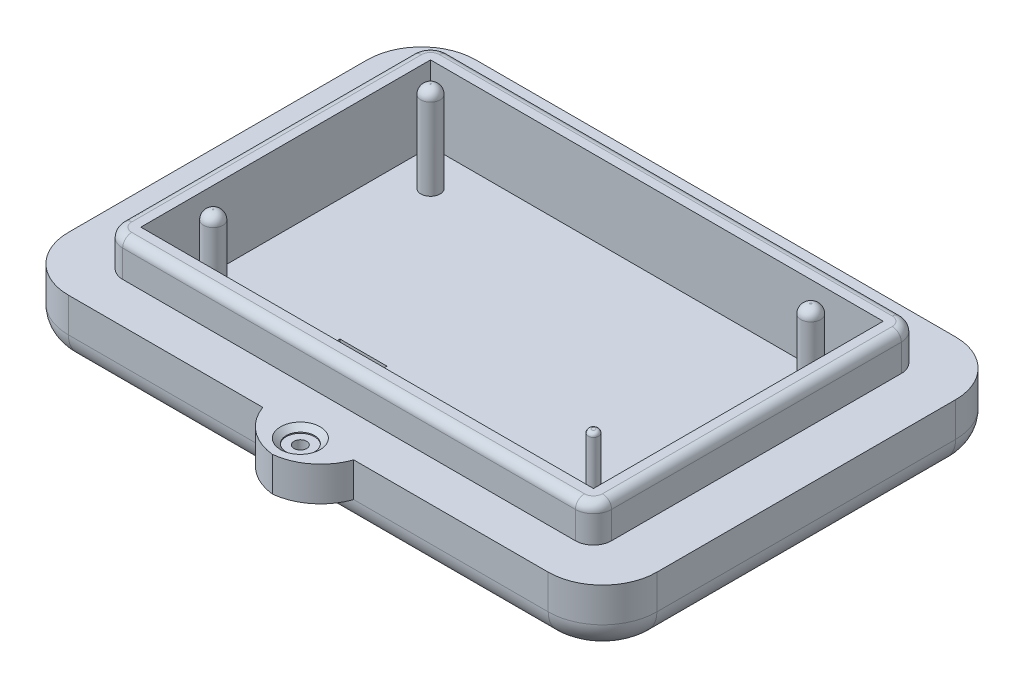
SolidWorks part; units mm, degrees
ref_plane "Front Plane" through (0, 0, 0) normal (0, 0, 1) x (1, 0, 0)
ref_plane "Top Plane" through (0, 0, 0) normal (0, 1, 0) x (1, 0, 0)
ref_plane "Right Plane" through (0, 0, 0) normal (1, 0, 0) x (0, 0, -1)
sketch "Sketch1" plane through (0, 0, 0) normal (0, 1, 0) x (1, 0, 0)
  line L1 (0, 0) -> (82.55, 0)
  line L2 (0, 0) -> (0, 57.15)
  line L3 (0, 57.15) -> (82.55, 57.15)
  line L4 (82.55, 0) -> (82.55, 57.15)
  dimension "D1" = 57.15
  dimension "D2" = 82.55
extrude "Boss-Extrude1" add sketch "Sketch1" along normal blind 8.636
fillet "Fillet2" radius 7.62 4 edges at (82.55, 4.318, -57.15) (82.55, 4.318, 0) (0, 4.318, 0) (0, 4.318, -57.15)
fillet "Fillet3" radius 3.81 8 edges at (80.3182, 0, -54.9182) (82.55, 0, -28.575) (80.3182, 0, -2.2318) (41.275, 0, 0) (2.2318, 0, -2.2318) (0, 0, -28.575) (2.2318, 0, -54.9182) (41.275, 0, -57.15)
sketch "Sketch2" plane through (0, 8.636, 0) normal (0, 1, 0) x (1, 0, 0)
  line L0 (0, 28.575) -> (82.55, 28.575) construction
  line L1 (0, 49.53) -> (0, 7.62) construction
  line L2 (82.55, 7.62) -> (82.55, 49.53) construction
  line L4 (9.525, 8.255) -> (73.025, 8.255)
  line L5 (9.525, 8.255) -> (9.525, 48.895)
  line L6 (9.525, 48.895) -> (73.025, 48.895)
  line L7 (73.025, 8.255) -> (73.025, 48.895)
  line L8 (9.525, 8.255) -> (73.025, 48.895) construction
  line L9 (9.525, 48.895) -> (73.025, 8.255) construction
  point P6 (41.275, 28.575)
  dimension "D1" = 40.64
  dimension "D2" = 63.5
extrude "Cut-Extrude1" cut sketch "Sketch2" against normal blind 5.461
sketch "Sketch4" plane through (0, 3.175, 0) normal (0, 1, 0) x (1, 0, 0)
  line L2 (9.525, 48.895) -> (9.525, 8.255) construction
  line L3 (73.025, 8.255) -> (73.025, 48.895) construction
  line L4 (66.879, 18.375) -> (54.279, 18.375)
  line L5 (66.879, 18.375) -> (66.879, 13.375)
  line L6 (66.879, 13.375) -> (54.279, 13.375)
  line L7 (54.279, 18.375) -> (54.279, 13.375)
  line L8 (66.879, 18.375) -> (54.279, 13.375) construction
  line L9 (66.879, 13.375) -> (54.279, 18.375) construction
  line L10 (9.525, 8.255) -> (73.025, 8.255) construction
  line L11 (33.147, 19.177) -> (26.543, 19.177)
  line L12 (33.147, 19.177) -> (33.147, 12.573)
  line L13 (33.147, 12.573) -> (26.543, 12.573)
  line L14 (26.543, 19.177) -> (26.543, 12.573)
  line L15 (33.147, 19.177) -> (26.543, 12.573) construction
  line L16 (33.147, 12.573) -> (26.543, 19.177) construction
  circle A0 centre (42.291, 16.129) radius 2.25
  point P7 (60.579, 15.875)
  point P15 (29.845, 15.875)
  dimension "D3" = 4.5
  dimension "D2" = 32.766
  dimension "D4" = 7.62
  dimension "D5" = 12.6
  dimension "D6" = 5
  dimension "D7" = 12.446
  dimension "D8" = 6.604
  dimension "D9" = 6.604
  dimension "D10" = 7.62
  dimension "D11" = 20.32
  dimension "D12" = 7.874
extrude "Cut-Extrude2" cut sketch "Sketch4" against normal blind 7.366
sketch "Sketch7" plane through (0, 8.636, 0) normal (0, 1, 0) x (1, 0, 0)
  line L14 (6.985, 51.435) -> (6.985, 5.715)
  line L15 (6.985, 5.715) -> (75.565, 5.715)
  line L16 (75.565, 5.715) -> (75.565, 51.435)
  line L17 (75.565, 51.435) -> (6.985, 51.435)
  line L18 (6.985, 51.435) -> (6.985, 5.715)
  line L19 (6.985, 5.715) -> (75.565, 5.715)
  line L20 (75.565, 5.715) -> (75.565, 51.435)
  line L21 (75.565, 51.435) -> (6.985, 51.435)
  dimension "D1" = 2.54
extrude "Boss-Extrude3" add sketch "Sketch7" along normal blind 5.08
sketch "Sketch8" plane through (0, 13.716, 0) normal (0, 1, 0) x (1, 0, 0)
  line L8 (73.025, 48.895) -> (9.525, 48.895)
  line L9 (9.525, 48.895) -> (9.525, 8.255)
  line L10 (9.525, 8.255) -> (73.025, 8.255)
  line L11 (73.025, 8.255) -> (73.025, 48.895)
  line L12 (73.025, 48.895) -> (9.525, 48.895)
  line L13 (9.525, 48.895) -> (9.525, 8.255)
  line L14 (9.525, 8.255) -> (73.025, 8.255)
  line L15 (73.025, 8.255) -> (73.025, 48.895)
  dimension "D1" = 2.54
extrude "Cut-Extrude3" cut sketch "Sketch8" against normal blind 5.08
sketch "Sketch5" plane through (0, 3.175, 0) normal (0, 1, 0) x (1, 0, 0)
  line L0 (9.525, 48.895) -> (9.525, 8.255) construction
  line L2 (73.025, 48.895) -> (9.525, 48.895) construction
  line L3 (9.525, 8.255) -> (73.025, 8.255) construction
  line L4 (73.025, 8.255) -> (73.025, 48.895) construction
  circle A0 centre (14.605, 43.815) radius 1.35
  circle A1 centre (14.605, 13.335) radius 1.35
  circle A2 centre (67.945, 43.815) radius 1.385
  circle A3 centre (67.945, 13.335) radius 0.75
  dimension "D5" = 2.7
  dimension "D6" = 2.7
  dimension "D7" = 1.5
  dimension "D8" = 2.77
  dimension "D11" = 5.08
  dimension "D1" = 5.08
  dimension "D2" = 5.08
  dimension "D3" = 5.08
  dimension "D4" = 5.08
  dimension "D9" = 5.08
  dimension "D10" = 5.08
  dimension "D12" = 5.08
extrude "Boss-Extrude4" add sketch "Sketch5" along normal blind 12.7
fillet "Fillet7" radius 1.27 3 edges at (14.605, 15.875, -11.985) (14.605, 15.875, -42.465) (67.945, 15.875, -42.43)
fillet "Fillet8" radius 2.54 4 edges at (75.565, 11.176, -51.435) (75.565, 11.176, -5.715) (6.985, 11.176, -5.715) (6.985, 11.176, -51.435)
sketch "Sketch9" plane through (0, 0, 0) normal (0, 0, 1) x (1, 0, 0)
  line L0 (41.275, 8.636) -> (41.275, 3.81) construction
  line L1 (7.62, 8.636) -> (74.93, 8.636) construction
  line L2 (7.62, 3.81) -> (74.93, 3.81) construction
  line L4 (47.6519, 8.636) -> (34.8981, 8.636)
  line L5 (47.6519, 8.636) -> (47.6519, 3.81)
  line L6 (47.6519, 3.81) -> (34.8981, 3.81)
  line L7 (34.8981, 8.636) -> (34.8981, 3.81)
  line L8 (47.6519, 8.636) -> (34.8981, 3.81) construction
  line L9 (47.6519, 3.81) -> (34.8981, 8.636) construction
  point P6 (41.275, 6.223)
extrude "Boss-Extrude5" add sketch "Sketch9" along normal blind 5.08
fillet "Fillet10" radius 7.62 2 edges at (47.6519, 6.223, 5.08) (34.8981, 6.223, 5.08)
fillet "Fillet11" radius 1.27 8 edges at (74.8211, 13.716, -50.6911) (75.565, 13.716, -28.575) (74.8211, 13.716, -6.4589) (41.275, 13.716, -5.715) (7.7289, 13.716, -6.4589) (7.7289, 13.716, -50.6911) (6.985, 13.716, -28.575) (41.275, 13.716, -51.435)
fillet "Fillet12" radius 0.508 1 edges at (67.945, 15.875, -12.585)
sketch "Sketch10" plane through (0, 8.636, 0) normal (0, 1, 0) x (1, 0, 0)
  line L0 (45.191, -3.4396) -> (37.359, -3.4396) construction
  line L1 (9.525, 5.715) -> (73.025, 5.715) construction
  line L2 (41.275, 5.715) -> (41.275, -5.0371) construction
  arc A0 (41.275, -5.0371) -> (47.6519, 0) centre (40.4677, 2.54) ccw construction
  arc A1 (34.8981, 0) -> (41.275, -5.0371) centre (42.0823, 2.54) ccw construction
  point P10 (41.275, -3.4396)
  point P14 (0, 0)
  point P15 (0, 0)
hole_wizard "CBORE for #0 Binding Head Machine Screw1" positions "Sketch14" profile "Sketch15" counterbore size "#0" standard "ANSI Inch" end condition through all
sketch "Sketch14" plane through (0, 8.636, 0) normal (0, 1, 0) x (1, 0, 0)
  point P0 (41.2755, -1.1127)
sketch "Sketch15" plane through (41.2755, 8.636, 1.1127) normal (1, 0, 0) x (0, 0, 1)
  line L0 (0, 0) -> (0, 8.636)
  line L1 (0, 8.636) -> (0.889, 8.636)
  line L3 (0.889, 8.636) -> (0.889, 0.8128)
  line L4 (1.985, 0.8128) -> (0.889, 0.8128)
  line L5 (1.985, 0.8128) -> (1.985, 0.6682)
  line L6 (1.985, 0.6682) -> (2.7813, 0)
  line L7 (2.7813, 0) -> (0, 0)
  line L8 (-1.985, 0.6682) -> (-2.7813, 0) construction
  line L11 (0, -6.35) -> (0, 107.95) construction
  dimension "Thru Hole Dia." = 1.778
  dimension "Thru Hole Depth" = 8.636
  dimension "C'Bore Dia." = 3.97
  dimension "C'Bore Depth" = 0.8128
  dimension "Near C'Sink Dia." = 5.5626
  dimension "Near C'Sink Angle" = 100
